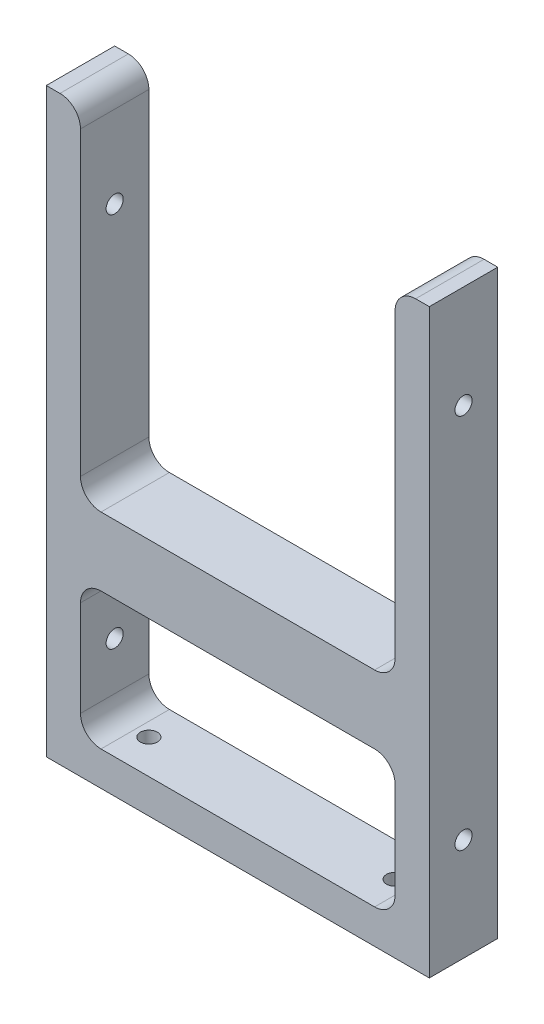
SolidWorks part; units mm, degrees
ref_plane "Спереди" through (0, 0, 0) normal (0, 0, 1) x (1, 0, 0)
ref_plane "Сверху" through (0, 0, 0) normal (0, 1, 0) x (1, 0, 0)
ref_plane "Справа" through (0, 0, 0) normal (1, 0, 0) x (0, 0, -1)
sketch "Эскиз1" plane through (0, 0, 0) normal (0, 0, 1) x (1, 0, 0)
  line L0 (-23, -17.5) -> (23, -17.5)
  line L1 (-28, 42.5) -> (-23, 42.5)
  line L2 (-28, 42.5) -> (-28, -42.5)
  line L3 (-28, -42.5) -> (28, -42.5)
  line L4 (28, 42.5) -> (28, -42.5)
  line L5 (-28, 42.5) -> (28, -42.5) construction
  line L6 (-28, -42.5) -> (28, 42.5) construction
  line L7 (23, 42.5) -> (28, 42.5)
  line L8 (-23, 42.5) -> (-23, -7.5)
  line L9 (-23, -37.5) -> (23, -37.5)
  line L10 (23, 42.5) -> (23, -7.5)
  line L13 (-23, -7.5) -> (23, -7.5)
  line L14 (-23, -17.5) -> (-23, -37.5)
  line L15 (23, -17.5) -> (23, -37.5)
  line L16 (-28, 0) -> (42.8015, 0) construction
  point P0 (0, 0)
  point P6 (0, 0)
  dimension "D1" = 56
  dimension "D2" = 85
  dimension "D3" = 5
  dimension "D4" = 5
  dimension "D5" = 10
  dimension "D6" = 20
  dimension "D7" = 5
extrude "Бобышка-Вытянуть1" add sketch "Эскиз1" along normal blind 10
fillet "Скругление1" radius 3 8 edges at (-23, -17.5, 5) (23, -17.5, 5) (23, -37.5, 5) (23, -7.5, 5) (23, 42.5, 5) (-23, -37.5, 5) (-23, -7.5, 5) (-23, 42.5, 5)
sketch "Эскиз2" plane through (0, -42.5, 0) normal (0, -1, 0) x (1, 0, 0)
  line L0 (-28, 5) -> (28, 5) construction
  line L1 (-28, 10) -> (-28, 0) construction
  line L2 (28, 10) -> (28, 0) construction
  line L3 (-18, 10) -> (-18, 0) construction
  line L4 (-28, 10) -> (28, 10) construction
  line L5 (-28, 0) -> (28, 0) construction
  line L6 (18, 10) -> (18, 0) construction
  dimension "D1" = 10
  dimension "D2" = 10
hole_wizard "Отверстие обработанное метчиком M3x0.51" positions "Эскиз4" profile "Эскиз3" tap size "M3x0.5" standard "Ansi Metric" end condition up to next
sketch "Эскиз4" plane through (0, -42.5, 0) normal (0, -1, 0) x (-1, 0, 0)
  line L0 (18, -10) -> (18, 0) construction
  line L1 (-18, -10) -> (-18, 0) construction
  point P0 (18, -5)
  point P4 (-18, -5)
sketch "Эскиз3" plane through (-18, -42.5, 5) normal (1, 0, 0) x (0, 0, -1)
  line L0 (0, 0) -> (0, 5)
  line L1 (0, 5) -> (1.25, 5)
  line L2 (1.25, 5) -> (1.25, 0)
  line L5 (1.25, 0) -> (0, 0)
  line L11 (0, -6.35) -> (0, 107.95) construction
  dimension "Диаметр проходного сверла" = 2.5
  dimension "Глубина проходного сверла" = 5
cosmetic thread "Отверстие резьбы1" parameters "D2"=3
cosmetic thread "Отверстие резьбы2" parameters "D2"=3
sketch "Эскиз5" plane through (28, 0, 0) normal (1, 0, 0) x (0, 0, -1)
  line L0 (-5, 42.5) -> (-5, -42.5) construction
  line L1 (-10, 42.5) -> (0, 42.5) construction
  line L2 (-10, -42.5) -> (0, -42.5) construction
  line L3 (0, 27.5) -> (-10, 27.5) construction
  line L4 (0, -42.5) -> (0, 42.5) construction
  line L5 (-10, -42.5) -> (-10, 42.5) construction
  line L6 (0, -27.5) -> (-10, -27.5) construction
  dimension "D1" = 15
  dimension "D2" = 15
hole_wizard "Отверстие обработанное метчиком M3x0.52" positions "Эскиз7" profile "Эскиз6" tap size "M3x0.5" standard "Ansi Metric" end condition through all
sketch "Эскиз7" plane through (28, 0, 0) normal (1, 0, 0) x (0, 0, -1)
  line L0 (0, 27.5) -> (-10, 27.5) construction
  line L1 (0, -27.5) -> (-10, -27.5) construction
  point P0 (-5, 27.5)
  point P4 (-5, -27.5)
sketch "Эскиз6" plane through (28, 27.5, 5) normal (0, 1, 0) x (0, 0, -1)
  line L0 (0, 0) -> (0, 56)
  line L1 (0, 56) -> (1.25, 56)
  line L2 (1.25, 56) -> (1.25, 0)
  line L5 (1.25, 0) -> (0, 0)
  line L11 (0, -6.35) -> (0, 107.95) construction
  dimension "Диаметр проходного сверла" = 2.5
  dimension "Глубина проходного сверла" = 56
cosmetic thread "Отверстие резьбы3" parameters "D2"=3
cosmetic thread "Отверстие резьбы4" parameters "D2"=3
